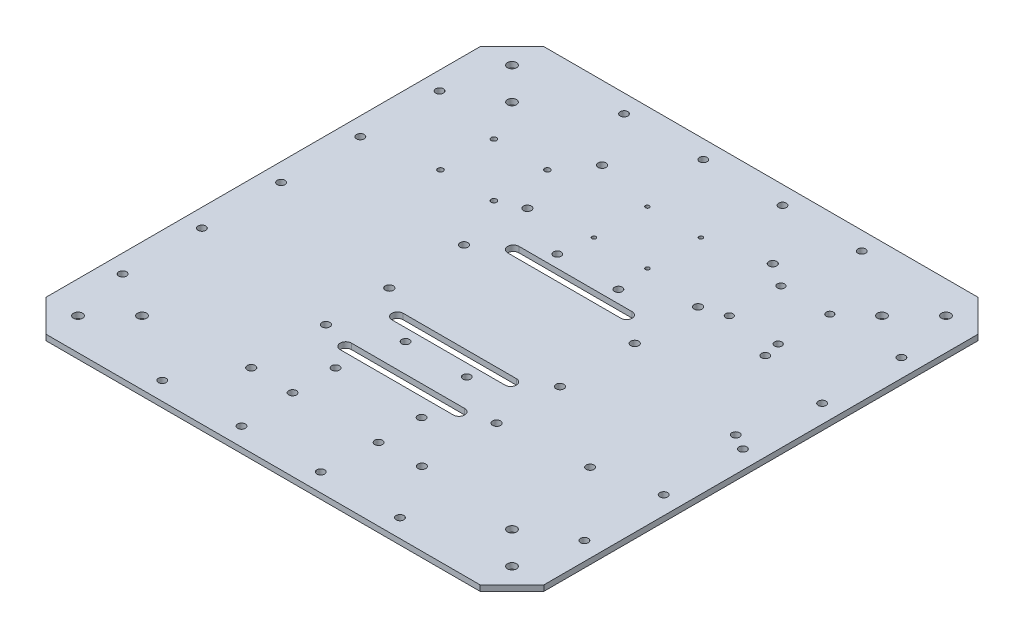
SolidWorks part; units mm, degrees
ref_plane "Front Plane" through (0, 0, 0) normal (0, 0, 1) x (1, 0, 0)
ref_plane "Top Plane" through (0, 0, 0) normal (0, 1, 0) x (1, 0, 0)
ref_plane "Right Plane" through (0, 0, 0) normal (1, 0, 0) x (0, 0, -1)
sketch "Sketch1" plane through (0, 0, 0) normal (0, 1, 0) x (1, 0, 0)
  line L0 (-160.4847, 61.5307) -> (-142.5242, 79.4912)
  line L1 (-160.4847, 79.4912) -> (118.9153, 79.4912)
  line L2 (-160.4847, 79.4912) -> (-160.4847, -199.9088)
  line L3 (-160.4847, -199.9088) -> (118.9153, -199.9088)
  line L4 (118.9153, 79.4912) -> (118.9153, -199.9088)
  line L5 (-20.7847, 79.4912) -> (-20.7847, -199.9088) construction
  line L6 (-160.4847, -60.2088) -> (118.9153, -60.2088) construction
  line L7 (118.9153, 61.5307) -> (100.9548, 79.4912)
  line L8 (118.9153, -181.9483) -> (100.9548, -199.9088)
  line L9 (-160.4847, -181.9483) -> (-142.5242, -199.9088)
  line L10 (-268.2478, 187.2542) -> (226.6783, -307.6719) construction
  line L11 (226.6783, -307.6719) -> (226.6783, 187.2542) construction
  line L12 (226.6783, 187.2542) -> (-268.2478, -307.6719) construction
  line L13 (-268.2478, -307.6719) -> (-268.2478, 187.2542) construction
  line L14 (-268.2478, 187.2542) -> (226.6783, 187.2542) construction
  line L15 (-268.2478, -307.6719) -> (226.6783, -307.6719) construction
  line L16 (-151.5045, 70.5109) -> (-268.2478, 187.2542) construction
  point P8 (-20.7847, 79.4912)
  point P11 (-160.4847, -60.2088)
  point P19 (118.9153, -60.2088)
  point P20 (-20.7847, -199.9088)
  point P22 (-151.5045, 70.5109)
  point P25 (-20.7847, -60.2088)
  point P26 (-20.7847, -60.2088)
  dimension "D1" = 279.4
  dimension "D2" = 279.4
  dimension "D3" = 165.1
  dimension "D4" = 25.4
extrude "Boss-Extrude1" add sketch "Sketch1" along normal blind 3.175 contours L2 L9 L3 L8 L4 L7 L1 L0 region at (-20.7847, 0, 60.2088)
sketch "Sketch2" plane through (0, 3.175, 0) normal (0, 1, 0) x (1, 0, 0)
  line L0 (-20.7847, 79.4912) -> (-20.7847, -287.8465) construction
  line L1 (-142.5242, 79.4912) -> (100.9548, 79.4912) construction
  line L2 (118.9153, -60.2088) -> (-158.2106, -60.2088) construction
  line L3 (118.9153, 61.5307) -> (118.9153, -181.9483) construction
  circle A0 centre (-38.0567, -17.5368) radius 2.159
  circle A1 centre (-3.7667, -17.5368) radius 2.159
  circle A2 centre (-38.0567, -102.6268) radius 2.159
  circle A3 centre (-3.7667, -102.6268) radius 2.159
  dimension "D5" = 4.318
  dimension "D6" = 4.318
  dimension "D7" = 4.318
  dimension "D8" = 4.318
  dimension "D1" = 17.272
  dimension "D2" = 34.29
  dimension "D3" = 85.09
  dimension "D4" = 42.672
extrude "Cut-Extrude1" cut sketch "Sketch2" against normal through all
sketch "Sketch4" plane through (0, 3.175, 0) normal (0, 1, 0) x (1, 0, 0)
  line L0 (-52.5347, -27.7088) -> (10.9653, -27.7088) construction
  line L1 (-52.5347, -24.5338) -> (10.9653, -24.5338)
  line L2 (-52.5347, -30.8838) -> (10.9653, -30.8838)
  line L3 (-52.5347, -92.7088) -> (10.9653, -92.7088) construction
  line L4 (-52.5347, -89.5338) -> (10.9653, -89.5338)
  line L5 (-52.5347, -95.8838) -> (10.9653, -95.8838)
  line L6 (118.9153, 61.5307) -> (118.9153, -181.9483) construction
  line L7 (-20.7847, -92.7088) -> (-20.7847, -198.1921) construction
  line L8 (-160.4847, -60.2088) -> (118.9153, -60.2088) construction
  line L9 (-160.4847, 61.5307) -> (-160.4847, -181.9483) construction
  line L14 (-52.5347, -121.708) -> (10.9653, -121.708) construction
  line L15 (-52.5347, -118.533) -> (10.9653, -118.533)
  line L16 (-52.5347, -124.883) -> (10.9653, -124.883)
  line L17 (-20.7847, -27.7088) -> (-20.7847, -92.7088) construction
  arc A0 (-52.5347, -24.5338) -> (-52.5347, -30.8838) centre (-52.5347, -27.7088) ccw
  arc A1 (10.9653, -30.8838) -> (10.9653, -24.5338) centre (10.9653, -27.7088) ccw
  arc A2 (-52.5347, -89.5338) -> (-52.5347, -95.8838) centre (-52.5347, -92.7088) ccw
  arc A3 (10.9653, -95.8838) -> (10.9653, -89.5338) centre (10.9653, -92.7088) ccw
  arc A7 (-52.5347, -118.533) -> (-52.5347, -124.883) centre (-52.5347, -121.708) ccw
  arc A8 (10.9653, -124.883) -> (10.9653, -118.533) centre (10.9653, -121.708) ccw
  point P2 (-20.7847, -27.7088)
  point P7 (-20.7847, -92.7088)
  point P14 (0, 0)
  point P18 (-20.7847, -60.2088)
  point P19 (-20.7847, -60.2088)
  point P33 (-20.7847, -121.708)
  dimension "D1" = 63.5
  dimension "D2" = 63.5
  dimension "D3" = 6.35
  dimension "D4" = 6.35
  dimension "D5" = 65
  dimension "D6" = 28.9992
  dimension "D8" = 63.5
  dimension "D9" = 6.35
extrude "Cut-Extrude2" cut sketch "Sketch4" against normal through all
sketch "Sketch7" plane through (0, 3.175, 0) normal (0, 1, 0) x (1, 0, 0)
  line L0 (-96.7307, 89.5196) -> (-96.7307, -24.0818) construction
  line L1 (-160.4847, -60.2088) -> (118.9153, -60.2088) construction
  line L2 (-160.4847, 61.5307) -> (-160.4847, -181.9483) construction
  line L3 (118.9153, 61.5307) -> (118.9153, -181.9483) construction
  line L4 (-20.7847, 79.4912) -> (-20.7847, -252.674) construction
  line L5 (-142.5242, 79.4912) -> (100.9548, 79.4912) construction
  circle A0 centre (-81.7447, 20.5632) radius 1.524
  circle A1 centre (-81.7447, -9.4088) radius 1.524
  circle A2 centre (-111.7167, -9.4088) radius 1.524
  circle A3 centre (-111.7167, 20.5632) radius 1.524
  dimension "D1" = 3.048
  dimension "D2" = 14.986
  dimension "D4" = 29.972
  dimension "D3" = 3.048
  dimension "D5" = 50.8
  dimension "D6" = 60.96
  dimension "D7" = 14.986
extrude "Cut-Extrude3" cut sketch "Sketch7" against normal through all
sketch "Sketch8" plane through (0, 3.175, 0) normal (0, 1, 0) x (1, 0, 0)
  line L0 (-142.5242, -199.9088) -> (100.9548, -199.9088) construction
  line L1 (118.9153, 61.5307) -> (118.9153, -181.9483) construction
  circle A0 centre (8.4253, -175.0168) radius 1.524
  circle A1 centre (8.4253, -144.5368) radius 1.524
  circle A2 centre (32.3013, -175.0168) radius 1.524
  circle A3 centre (32.3013, -144.5368) radius 1.524
  dimension "D1" = 3.048
  dimension "D2" = 30.48
  dimension "D3" = 23.876
  dimension "D4" = 24.892
  dimension "D5" = 86.614
extrude "Cut-Extrude4" [suppressed] cut sketch "Sketch8" against normal through all and the other way through all
sketch "Sketch10" plane through (0, 0, 0) normal (0, -1, 0) x (1, 0, 0)
  line L0 (-142.5242, 199.9088) -> (100.9548, 199.9088) construction
  line L1 (-20.7847, 199.9088) -> (-20.7847, 128.7119) construction
  line L2 (-52.5347, 124.883) -> (10.9653, 124.883) construction
  circle A0 centre (-44.9147, 159.173) radius 2.159
  circle A1 centre (3.3453, 159.173) radius 2.159
  circle A2 centre (-44.9147, 135.043) radius 2.159
  circle A3 centre (3.3453, 135.043) radius 2.159
  dimension "D1" = 4.318
  dimension "D2" = 48.26
  dimension "D4" = 10.16
  dimension "D6" = 4.318
  dimension "D7" = 4.318
  dimension "D8" = 4.318
  dimension "D3" = 24.13
  dimension "D5" = 24.13
extrude "Cut-Extrude6" cut sketch "Sketch10" against normal through all
sketch "Sketch9" plane through (0, 0, 0) normal (0, -1, 0) x (-1, 0, 0)
  line L1 (160.4847, -60.2088) -> (-327.4314, -60.2088) construction
  line L2 (-53.8913, -43.6513) -> (-53.8913, -126.5783) construction
  line L3 (20.7847, 79.4912) -> (20.7847, -331.7119) construction
  line L4 (142.5242, 79.4912) -> (-100.9548, 79.4912) construction
  line L7 (160.4847, 61.5307) -> (160.4847, -181.9483) construction
  circle A0 centre (-40.1753, 0.7512) radius 2.032
  circle A1 centre (-67.6073, 0.7512) radius 2.032
  circle A2 centre (-40.1753, 29.7072) radius 2.032
  circle A3 centre (-67.6073, 29.7072) radius 2.032
  point P10 (-113.1027, 4.7869)
  dimension "D1" = 4.064
  dimension "D9" = 4.064
  dimension "D2" = 60.96
  dimension "D3" = 28.956
  dimension "D4" = 60.96
  dimension "D8" = 13.716
extrude "Cut-Extrude5" cut sketch "Sketch9" against normal through all
sketch "Sketch13" plane through (0, 0, 0) normal (0, -1, 0) x (1, 0, 0)
  line L0 (-20.7847, -79.4912) -> (-20.7847, 261.4711) construction
  line L1 (-142.5242, -79.4912) -> (100.9548, -79.4912) construction
  line L2 (-160.4847, 60.2088) -> (239.2508, 60.2088) construction
  line L3 (-160.4847, -61.5307) -> (-160.4847, 181.9483) construction
  circle A0 centre (-35.7847, -0.7512) radius 1.1
  circle A1 centre (-35.7847, -30.7512) radius 1.1
  circle A2 centre (-5.7847, -30.7512) radius 1.1
  circle A3 centre (-5.7847, -0.7512) radius 1.1
  dimension "D1" = 2.2
  dimension "D2" = 2.2
  dimension "D3" = 30
  dimension "D4" = 15
  dimension "D5" = 60.96
extrude "Cut-Extrude8" cut sketch "Sketch13" against normal through all
sketch "Sketch14" plane through (0, 0, 0) normal (0, -1, 0) x (1, 0, 0)
  line L0 (-20.7847, 199.9088) -> (-20.7847, -154.5354) construction
  line L1 (-142.5242, 199.9088) -> (100.9548, 199.9088) construction
  line L2 (-160.4847, 60.2088) -> (331.9066, 60.2088) construction
  line L3 (-160.4847, -61.5307) -> (-160.4847, 181.9483) construction
  line L4 (-160.4847, 181.9483) -> (-142.5242, 199.9088) construction
  line L5 (-268.2478, -187.2542) -> (226.6783, 307.6719) construction
  line L6 (-268.2478, -187.2542) -> (226.6783, -187.2542) construction
  line L7 (-268.2478, -187.2542) -> (-268.2478, 307.6719) construction
  line L8 (-160.4847, 181.9483) -> (-142.5242, 199.9088) construction
  line L9 (-151.5045, 190.9286) -> (-83.1439, 122.568) construction
  line L10 (-268.2478, 307.6719) -> (226.6783, 307.6719) construction
  line L11 (226.6783, -187.2542) -> (226.6783, 307.6719) construction
  line L12 (226.6783, -187.2542) -> (-268.2478, 307.6719) construction
  line L14 (-160.4847, -61.5307) -> (-142.5242, -79.4912) construction
  line L21 (-268.2478, -187.2542) -> (-151.5045, -70.5109) construction
  line L22 (109.935, -70.5109) -> (226.6783, -187.2542) construction
  line L23 (118.9153, -61.5307) -> (100.9548, -79.4912) construction
  line L24 (109.935, 190.9286) -> (226.6783, 307.6719) construction
  line L25 (118.9153, 181.9483) -> (100.9548, 199.9088) construction
  line L26 (-268.2478, 307.6719) -> (-151.5045, 190.9286) construction
  circle A1 centre (-142.5242, 181.9483) radius 2.54
  circle A3 centre (-124.5637, 163.9878) radius 2.54
  circle A4 centre (82.9942, 163.9878) radius 2.54
  circle A7 centre (100.9548, 181.9483) radius 2.54
  circle A8 centre (-142.5242, -61.5307) radius 2.54
  circle A11 centre (-124.5637, -43.5701) radius 2.54
  circle A14 centre (100.9548, -61.5307) radius 2.54
  circle A15 centre (82.9942, -43.5701) radius 2.54
  point P8 (-20.7847, 60.2088)
  point P30 (226.6783, 60.2088)
  point P33 (-151.5045, -70.5109)
  point P36 (-20.7847, -187.2542)
  dimension "D3" = 5.08
  dimension "D6" = 5.08
  dimension "D1" = 12.7
  dimension "D2" = 165.1
  dimension "D9" = 25.4
extrude "Cut-Extrude9" cut sketch "Sketch14" against normal through all
sketch "Sketch15" plane through (0, 0, 0) normal (0, -1, 0) x (1, 0, 0)
  line L0 (-20.7847, 199.9088) -> (-20.7847, 125.875) construction
  line L1 (-142.5242, 199.9088) -> (100.9548, 199.9088) construction
  line L2 (-160.4847, 60.2088) -> (75.4631, 60.2088) construction
  line L3 (-160.4847, -61.5307) -> (-160.4847, 181.9483) construction
  circle A0 centre (-43.0097, 189.7488) radius 2.159
  circle A1 centre (-87.4597, 189.7488) radius 2.159
  circle A2 centre (-150.3247, 60.2088) radius 2.159
  circle A3 centre (-150.3247, 104.6588) radius 2.159
  circle A4 centre (-150.3247, 149.1088) radius 2.159
  circle A5 centre (108.7553, 149.1088) radius 2.159
  circle A6 centre (108.7553, 104.6588) radius 2.159
  circle A7 centre (108.7553, 60.2088) radius 2.159
  circle A8 centre (45.8903, 189.7488) radius 2.159
  circle A9 centre (1.4403, 189.7488) radius 2.159
  circle A10 centre (1.4403, -69.3312) radius 2.159
  circle A11 centre (45.8903, -69.3312) radius 2.159
  circle A12 centre (108.7553, 15.7588) radius 2.159
  circle A13 centre (108.7553, -28.6912) radius 2.159
  circle A14 centre (-150.3247, -28.6912) radius 2.159
  circle A15 centre (-150.3247, 15.7588) radius 2.159
  circle A16 centre (-87.4597, -69.3312) radius 2.159
  circle A17 centre (-43.0097, -69.3312) radius 2.159
  dimension "D3" = 4.318
  dimension "D4" = 4.318
  dimension "D8" = 4.318
  dimension "D9" = 4.318
  dimension "D10" = 4.318
  dimension "D1" = 22.225
  dimension "D2" = 44.45
  dimension "D5" = 10.16
  dimension "D6" = 44.45
  dimension "D7" = 44.45
  dimension "D11" = 10.16
extrude "Cut-Extrude10" cut sketch "Sketch15" against normal through all
sketch "Sketch16" plane through (0, 0, 0) normal (0, -1, 0) x (-1, 0, 0)
  line L0 (20.7847, 79.4912) -> (20.7847, -323.0503) construction
  line L1 (-49.3193, -101.9918) -> (-89.9593, -101.9918)
  line L2 (-49.3193, -101.9918) -> (-49.3193, -18.4258)
  line L3 (-49.3193, -18.4258) -> (-89.9593, -18.4258)
  line L4 (-89.9593, -101.9918) -> (-89.9593, -18.4258)
  line L6 (142.5242, 79.4912) -> (-100.9548, 79.4912) construction
  line L7 (160.4847, -60.2088) -> (-312.3855, -60.2088) construction
  line L8 (160.4847, 61.5307) -> (160.4847, -181.9483) construction
  circle A0 centre (-74.7193, -111.8978) radius 2.159
  circle A1 centre (-69.6393, -8.5198) radius 2.159
  circle A2 centre (-99.8653, -55.3418) radius 2.159
  point P18 (-89.9593, -60.2088)
  dimension "D3" = 9.906
  dimension "D4" = 9.906
  dimension "D5" = 9.906
  dimension "D6" = 15.24
  dimension "D7" = 20.32
  dimension "D8" = 46.65
  dimension "D9" = 4.318
  dimension "D10" = 4.318
  dimension "D11" = 4.318
  dimension "D1" = 83.566
  dimension "D2" = 40.64
  dimension "D12" = 120.65
  dimension "D13" = 0
extrude "Cut-Extrude11" cut sketch "Sketch16" against normal through all contours A2 | A0 | A1
sketch "Sketch17" plane through (0, 3.175, 0) normal (0, 1, 0) x (1, 0, 0)
  line L2 (-20.7847, 79.4912) -> (-20.7847, -395.818) construction
  line L3 (-142.5242, 79.4912) -> (100.9548, 79.4912) construction
  line L4 (118.9153, -60.2088) -> (-127.1454, -60.2088) construction
  line L5 (118.9153, 61.5307) -> (118.9153, -181.9483) construction
  circle A12 centre (27.0943, -158.6338) radius 2.2225
  circle A13 centre (-68.6637, -158.6338) radius 2.2225
  circle A14 centre (27.0943, -116.7238) radius 2.2225
  circle A15 centre (-68.6637, -116.7238) radius 2.2225
  circle A16 centre (27.0943, -81.1638) radius 2.2225
  circle A17 centre (-68.6637, -81.1638) radius 2.2225
  circle A18 centre (27.0943, -39.2538) radius 2.2225
  circle A19 centre (-68.6637, -39.2538) radius 2.2225
  circle A20 centre (27.0943, -3.6938) radius 2.2225
  circle A21 centre (-68.6637, -3.6938) radius 2.2225
  circle A22 centre (27.0943, 38.2162) radius 2.2225
  circle A23 centre (-68.6637, 38.2162) radius 2.2225
  circle A24 centre (-68.6637, 38.2162) radius 2.2225
  circle A25 centre (27.0943, 38.2162) radius 2.2225
  circle A26 centre (-68.6637, -3.6938) radius 2.2225
  circle A27 centre (27.0943, -3.6938) radius 2.2225
  circle A28 centre (-68.6637, -39.2538) radius 2.2225
  circle A29 centre (27.0943, -39.2538) radius 2.2225
  circle A30 centre (-68.6637, -81.1638) radius 2.2225
  circle A31 centre (27.0943, -81.1638) radius 2.2225
  circle A32 centre (-68.6637, -116.7238) radius 2.2225
  circle A33 centre (27.0943, -116.7238) radius 2.2225
  circle A34 centre (-68.6637, -158.6338) radius 2.2225
  dimension "D1" = 4.445
  dimension "D2" = 4.445
  dimension "D3" = 4.445
  dimension "D4" = 4.445
  dimension "D5" = 4.445
  dimension "D6" = 4.445
  dimension "D7" = 4.445
  dimension "D8" = 4.445
  dimension "D9" = 4.445
  dimension "D10" = 4.445
  dimension "D11" = 4.445
  dimension "D12" = 4.445
  dimension "D25" = 56.515
  dimension "D24" = 56.515
  dimension "D13" = 95.758
  dimension "D14" = 41.91
  dimension "D15" = 95.758
  dimension "D16" = 41.91
  dimension "D17" = 95.758
  dimension "D18" = 41.91
  dimension "D19" = 47.879
  dimension "D20" = 47.879
  dimension "D21" = 47.879
  dimension "D22" = 20.955
extrude "Cut-Extrude13" cut sketch "Sketch17" against normal through all contours A23 | A22 | A20 | A21 | A18 | A19 | A17 | A16 | A12 | A14 | A15 | A13
sketch "Sketch18" [suppressed] plane through (0, 3.175, 0) normal (0, 1, 0) x (1, 0, 0)
  line L1 (-142.5242, -199.9088) -> (-160.4847, -181.9483)
  line L2 (-142.5242, -199.9088) -> (-106.6032, -163.9878)
  line L3 (-106.6032, -163.9878) -> (-124.5637, -146.0273)
  line L4 (-160.4847, -181.9483) -> (-124.5637, -146.0273)
  line L5 (-20.7847, 79.4912) -> (-20.7847, -264.9481) construction
  line L6 (-142.5242, 79.4912) -> (100.9548, 79.4912) construction
  line L7 (118.9153, -60.2088) -> (-155.4453, -60.2088) construction
  line L8 (118.9153, 61.5307) -> (118.9153, -181.9483) construction
  line L9 (-160.4847, 61.5307) -> (-124.5637, 25.6096)
  line L10 (-106.6032, 43.5701) -> (-124.5637, 25.6096)
  line L11 (-142.5242, 79.4912) -> (-106.6032, 43.5701)
  line L12 (-142.5242, 79.4912) -> (-160.4847, 61.5307)
  line L13 (100.9548, 79.4912) -> (118.9153, 61.5307)
  line L14 (100.9548, 79.4912) -> (65.0337, 43.5701)
  line L15 (65.0337, 43.5701) -> (82.9942, 25.6096)
  line L16 (118.9153, 61.5307) -> (82.9942, 25.6096)
  line L17 (118.9153, -181.9483) -> (82.9942, -146.0273)
  line L18 (65.0337, -163.9878) -> (82.9942, -146.0273)
  line L19 (100.9548, -199.9088) -> (65.0337, -163.9878)
  line L20 (100.9548, -199.9088) -> (118.9153, -181.9483)
  line L21 (-142.5242, -181.9483) -> (-124.5637, -163.9878) construction
  line L22 (-160.4847, -181.9483) -> (-142.5242, -199.9088) construction
  line L23 (-160.4847, -181.9483) -> (-142.5242, -199.9088) construction
  circle A2 centre (-124.5637, -163.9878) radius 2.54 construction
  circle A3 centre (-142.5242, -181.9483) radius 2.54 construction
  circle A4 centre (-124.5637, -163.9878) radius 2.54 construction
  circle A5 centre (-142.5242, -181.9483) radius 2.54 construction
  point P12 (-151.5045, -190.9286)
  point P33 (-151.5045, -190.9286)
  dimension "D1" = 50.8
  dimension "D2" = 25.4
